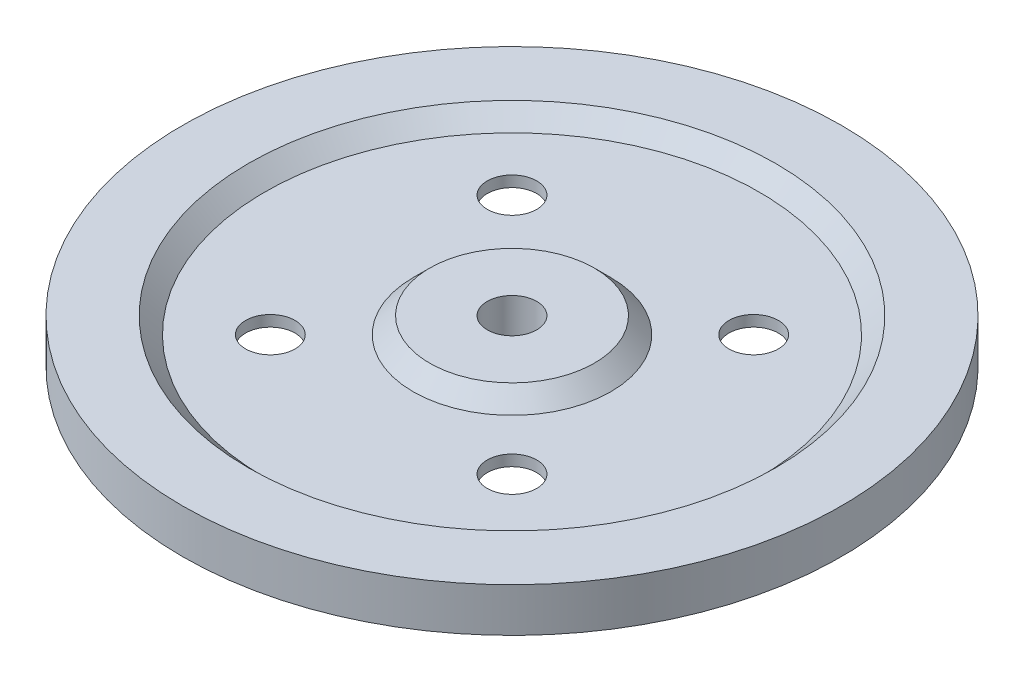
SolidWorks part; units mm, degrees
ref_plane "Front Plane" through (0, 0, 0) normal (0, 0, 1) x (1, 0, 0)
ref_plane "Top Plane" through (0, 0, 0) normal (0, 1, 0) x (1, 0, 0)
ref_plane "Right Plane" through (0, 0, 0) normal (1, 0, 0) x (0, 0, -1)
sketch "Sketch1" plane through (0, 0, 0) normal (0, 1, 0) x (1, 0, 0)
  circle A0 centre (0, 0) radius 300
  circle A1 centre (0, 0) radius 225
  circle A2 centre (0, 0) radius 90
  dimension "D1" = 600
  dimension "D2" = 450
  dimension "D3" = 180
extrude "Boss-Extrude1" add sketch "Sketch1" along normal mid plane 40 contours A0 A1 | A2 region at (-291.5147, 0, 0) region at (0, 0, 0)
sketch "Sketch3" plane through (0, 0, 0) normal (0, 1, 0) x (1, 0, 0)
  circle A0 centre (0, 0) radius 225
  dimension "D1" = 450
extrude "Boss-Extrude3" add sketch "Sketch3" along normal mid plane 10
chamfer "Chamfer2" distance 15 angle 45 4 edges at (0, -20, 90) (0, -20, 225) (0, 20, 225) (0, 20, 90)
sketch "Sketch4" plane through (0, 0, 0) normal (0, 1, 0) x (1, 0, 0)
  line L0 (0, 316.3862) -> (0, -327.5175) construction
  line L1 (-372.4709, 0) -> (324.5206, 0) construction
  circle A0 centre (0, 0) radius 22.5
  circle A1 centre (-110, 110) radius 22.5
  circle A2 centre (110, 110) radius 22.5
  circle A3 centre (110, -110) radius 22.5
  circle A4 centre (-110, -110) radius 22.5
  dimension "D1" = 45
  dimension "D2" = 45
  dimension "D3" = 110
  dimension "D4" = 110
extrude "Cut-Extrude1" cut sketch "Sketch4" against normal through all both and the other way through all
